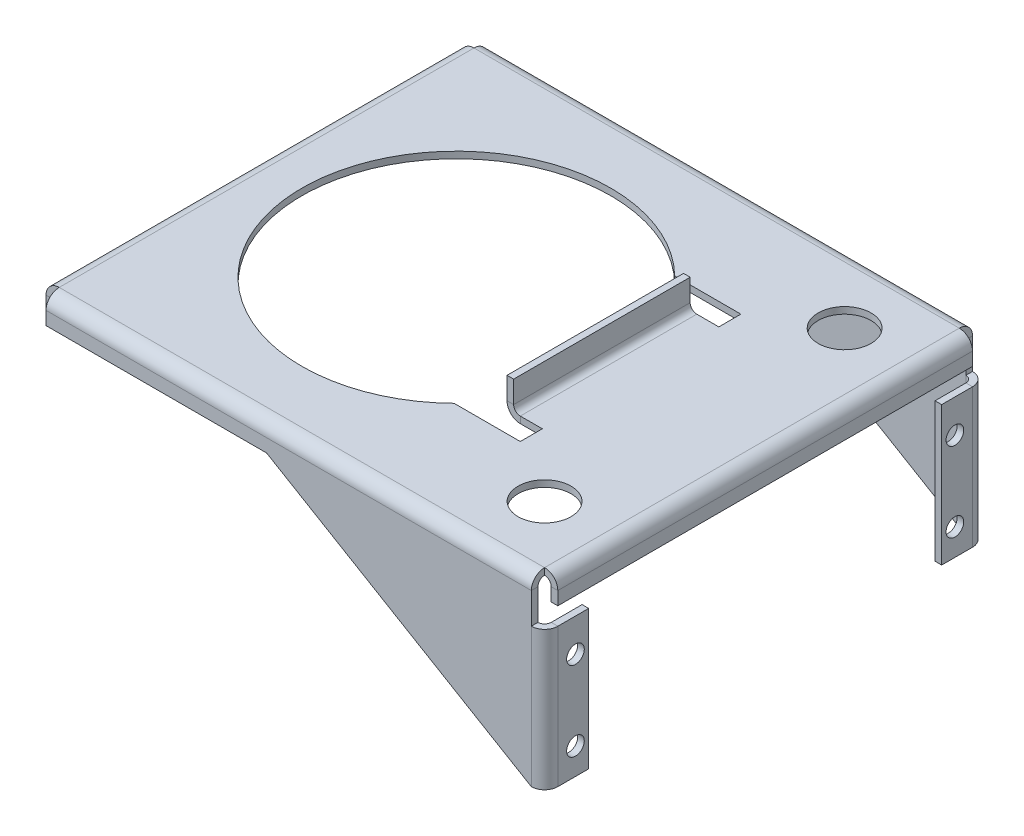
SolidWorks part; units mm, degrees
note: The reader was unsure of these and kept them because the rebuilt part matched: flange length of "Edge-Flange1", "Edge-Flange2", "Edge-Flange3", "Edge-Flange4".
ref_plane "Front Plane" through (0, 0, 0) normal (0, 0, 1) x (1, 0, 0)
ref_plane "Top Plane" through (0, 0, 0) normal (0, 1, 0) x (1, 0, 0)
ref_plane "Right Plane" through (0, 0, 0) normal (1, 0, 0) x (0, 0, -1)
sketch "Sketch1" plane through (0, 0, 0) normal (0, 1, 0) x (1, 0, 0)
  line L0 (-988, 0) -> (49012, 0) construction
  line L1 (-43, -50) -> (67, -50)
  line L2 (-43, -50) -> (-43, 50)
  line L3 (-43, 50) -> (67, 50)
  line L4 (67, -50) -> (67, 50)
  line L5 (-43, -50) -> (67, 50) construction
  line L6 (-43, 50) -> (67, -50) construction
  line L7 (24.4949, -25) -> (39.4949, -25)
  line L9 (24.4949, 25) -> (39.4949, 25)
  line L10 (39.4949, -25) -> (39.4949, -20)
  line L13 (39.4949, 20) -> (31.4949, 20)
  line L14 (31.4949, 20) -> (31.4949, -20)
  line L15 (31.4949, -20) -> (39.4949, -20)
  line L16 (39.4949, 20) -> (39.4949, 25)
  arc A0 (24.4949, 25) -> (24.4949, -25) centre (0, 0) ccw
  point P3 (12, 0)
  point P9 (31.9949, 0)
  dimension "D1" = 70
  dimension "D2" = 100
  dimension "D3" = 110
  dimension "D4" = 43
  dimension "D5" = 50
  dimension "D6" = 15
  dimension "D7" = 8
  dimension "D8" = 5
base flange "Base-Flange1" sketch "Sketch1" thickness 1.5 reverse thickness direction no parameters "D1"=1.5
edge flange "Edge-Flange1" sketch "Sketch12" flange angle 90 flange length 41.5 flange position material inside bend radius 1.5 thickness 1.5 parameters "D6"=10
sketch "Sketch12" plane through (0, -1.5, 50) normal (0, 0, -1) x (1, 0, 0)
  line L2 (-43, 0) -> (-43, 4.5)
  line L4 (67, 40) -> (67, 0)
  line L5 (67, 0) -> (-43, 0) construction
  line L6 (67, 0) -> (-43, 0)
  line L7 (-43, 4.5) -> (7, 4.5)
  line L9 (67, -1.5) -> (-43, -1.5) construction
  line L10 (7, 4.5) -> (67, 40)
  dimension "D1" = 6
  dimension "D2" = 41.5
  dimension "D3" = 50
bend "EdgeBend1" bend radius 1.5 bend angle 90 parameters "D5"=1
edge flange "Edge-Flange2" sketch "Sketch15" flange angle 90 flange length 10 flange position bend outside bend radius 1.5 thickness 1.5 parameters "D6"=10
sketch "Sketch15" plane through (67, 0, 48.5) normal (1, 0, 0) x (0, -1, 0)
  line L2 (10, 0) -> (10, 8.5)
  line L3 (10, 8.5) -> (41.5, 8.5)
  line L4 (41.5, 8.5) -> (41.5, 0)
  line L19 (3, 0) -> (41.5, 0) construction
  line L20 (10, 0) -> (41.5, 0)
  line L22 (0, 1.5) -> (0, 98.5) construction
  dimension "D1" = 10
bend "EdgeBend2" bend radius 1.5 bend angle 90 parameters "D5"=2
hole_wizard "Ø4.0 (4) Diameter Hole1" positions "Sketch16" profile "Sketch17" hole size "Ø4.0" standard "ISO" end condition up to next
sketch "Sketch16" plane through (70, 0, 0) normal (1, 0, 0) x (0, 0, -1)
  line L0 (-47, -41.5) -> (-40, -41.5) construction
  line L1 (-40, -41.5) -> (-40, -10) construction
  point P0 (-43, -17.5)
  point P2 (-43, -35.5)
  point P5 (0, 0)
  dimension "D1" = 6
  dimension "D2" = 18
  dimension "D3" = 3
sketch "Sketch17" plane through (70, -17.5, 43) normal (0, 1, 0) x (0, 0, -1)
  line L0 (0, 0) -> (0, 1.5)
  line L1 (0, 1.5) -> (2, 1.5)
  line L2 (2, 1.5) -> (2, 0)
  line L5 (2, 0) -> (0, 0)
  line L11 (0, -6.35) -> (0, 107.95) construction
  dimension "Thru Hole Dia." = 4
  dimension "Thru Hole Depth" = 1.5
mirror "Mirror1" about plane through (0, 0, 0) normal (0, 0, 1) of "Edge-Flange1", "Edge-Flange2", "Ø4.0 (4) Diameter Hole1"
bend "MirrorBend1" bend radius 1.5 bend angle 90 parameters "D5"=3
bend "MirrorBend2" bend radius 1.5 bend angle 90 parameters "D5"=4
edge flange "Edge-Flange3" sketch "Sketch22" flange profiles "Sketch22", "Sketch24" flange angle 90 flange length 6 flange position bend outside bend radius 1.5 thickness 1.5 parameters "D6"=10, "D8"=1
sketch "Sketch22" plane through (67, -1.5, 0) normal (1, 0, 0) x (0, 0, 1)
  line L2 (-47, 0) -> (-47, 4.5)
  line L3 (-47, 4.5) -> (47, 4.5)
  line L4 (47, 4.5) -> (47, 0)
  line L7 (47, 0) -> (-47, 0) construction
  line L8 (47, 0) -> (-47, 0)
sketch "Sketch24" plane through (-43, -1.5, 0) normal (-1, 0, 0) x (0, 0, -1)
  line L0 (47, 0) -> (-47, 0) construction
  line L1 (47, 0) -> (-47, 0)
  line L2 (-47, 0) -> (-47, 4.5)
  line L3 (-47, 4.5) -> (47, 4.5)
  line L4 (47, 4.5) -> (47, 0)
bend "EdgeBend3" bend radius 1.5 bend angle 90 parameters "D5"=5
bend "EdgeBend4" bend radius 1.5 bend angle 90 parameters "D5"=7
hole_wizard "Ø12.0 (12) Diameter Hole1" positions "Sketch18" profile "Sketch19" hole size "Ø12.0" standard "ISO" end condition up to next
sketch "Sketch18" plane through (0, 0, 0) normal (0, 1, 0) x (1, 0, 0)
  line L0 (-1000, 0) -> (49000, 0) construction
  line L1 (67, -50) -> (-43, -50) construction
  line L2 (70, -47) -> (70, 47) construction
  point P0 (54, 34)
  point P2 (54, -34)
  dimension "D1" = 16
  dimension "D2" = 16
sketch "Sketch19" plane through (54, 0, -34) normal (1, 0, 0) x (0, 0, 1)
  line L0 (0, 0) -> (0, 1.5)
  line L1 (0, 1.5) -> (6, 1.5)
  line L2 (6, 1.5) -> (6, 0)
  line L5 (6, 0) -> (0, 0)
  line L11 (0, -6.35) -> (0, 107.95) construction
  dimension "Thru Hole Dia." = 12
  dimension "Thru Hole Depth" = 1.5
edge flange "Edge-Flange4" sketch "Sketch27" flange angle 90 flange length 6.5 flange position material inside bend radius 1.5 thickness 1.5 parameters "D6"=10
sketch "Sketch27" plane through (31.4949, 0, 0) normal (-1, 0, 0) x (0, 0, 1)
  line L2 (-20, 0) -> (-20, 6.5)
  line L3 (-20, 6.5) -> (20, 6.5)
  line L4 (20, 6.5) -> (20, 0)
  line L7 (20, 0) -> (-20, 0) construction
  line L8 (20, 0) -> (-20, 0)
bend "EdgeBend5" bend radius 1.5 bend angle 90 parameters "D5"=8
sketch "Bend-Lines1" [suppressed] plane through (0, 0, 0) normal (0, 1, 0) x (1, 0, 0)
sketch "Bounding-Box1" [suppressed] plane through (0, 0, 0) normal (0, 1, 0) x (1, 0, 0)
sheet metal parameters "Sheet-Metal1" thickness 1.5 parameters "D1"=2.5
flat pattern "Flat-Pattern1" [suppressed]
sketch "Bend-Lines2" plane through (0, 0, 0) normal (0, 1, 0) x (1, 0, 0)
sketch3d "Bounding-Box2" [suppressed]
  line L0 (-67, 50, 0) -> (43, 50, 0) construction
  line L1 (-67, -50, 0) -> (43, -50, 0) construction
  line L2 (-67, 50, 0) -> (-67, -50, 0) construction
  line L3 (43, 50, 0) -> (43, -50, 0) construction
sheet metal parameters "Sheet-Metal2" thickness 1.5 parameters "D1"=2.5
flat pattern "Flat-Pattern1"
sketch "Bend-Lines2" plane through (0, 0, 0) normal (0, 1, 0) x (1, 0, 0)
  line L0 (-43, -48.5525) -> (67, -48.5525) construction
  line L1 (-43, -48.5525) -> (67, -48.5525) construction
sketch3d "Bounding-Box2" [suppressed]
  line L0 (-43, -88.6051, 0) -> (-43, 50, 0) construction
  line L1 (67, -88.6051, 0) -> (67, 50, 0) construction
  line L2 (-43, -88.6051, 0) -> (67, -88.6051, 0) construction
  line L3 (-43, 50, 0) -> (67, 50, 0) construction
bend of the flat pattern "Flatten-<EdgeBend1>1"
sheet metal parameters "Sheet-Metal3" thickness 1.5 parameters "D1"=2.5
flat pattern "Flat-Pattern1"
sketch "Bend-Lines2" plane through (0, 0, 0) normal (0, 1, 0) x (1, 0, 0)
  line L0 (-43, -48.7671) -> (67, -48.7671) construction
  line L1 (-43, -48.7671) -> (67, -48.7671) construction
  line L2 (65.7671, -88.1652) -> (65.7671, -57.5343) construction
  line L3 (65.7671, -88.1652) -> (65.7671, -57.5343) construction
sketch3d "Bounding-Box2" [suppressed]
  line L0 (-43, -89.0343, 0) -> (-43, 50, 0) construction
  line L1 (74.5343, -89.0343, 0) -> (74.5343, 50, 0) construction
  line L2 (-43, -89.0343, 0) -> (74.5343, -89.0343, 0) construction
  line L3 (-43, 50, 0) -> (74.5343, 50, 0) construction
bend of the flat pattern "Flatten-<EdgeBend1>1"
bend of the flat pattern "Flatten-<EdgeBend2>1"
sheet metal parameters "Sheet-Metal4" thickness 1.5 parameters "D1"=2.5
flat pattern "Flat-Pattern1"
sketch "Bend-Lines2" plane through (0, 0, 0) normal (0, 1, 0) x (1, 0, 0)
  line L0 (-43, -48.7671) -> (67, -48.7671) construction
  line L1 (-43, -48.7671) -> (67, -48.7671) construction
  line L2 (65.7671, -88.1652) -> (65.7671, -57.5343) construction
  line L3 (65.7671, -88.1652) -> (65.7671, -57.5343) construction
sketch3d "Bounding-Box2" [suppressed]
  line L0 (-43, -89.0343, 0) -> (-43, 50, 0) construction
  line L1 (74.5343, -89.0343, 0) -> (74.5343, 50, 0) construction
  line L2 (-43, -89.0343, 0) -> (74.5343, -89.0343, 0) construction
  line L3 (-43, 50, 0) -> (74.5343, 50, 0) construction
bend of the flat pattern "Flatten-<EdgeBend1>1"
bend of the flat pattern "Flatten-<EdgeBend2>1"
sheet metal parameters "Sheet-Metal5" thickness 1.5 parameters "D1"=2.5
flat pattern "Flat-Pattern1"
sketch "Bend-Lines2" plane through (0, 0, 0) normal (0, 1, 0) x (1, 0, 0)
  line L0 (-43, -48.7671) -> (67, -48.7671) construction
  line L1 (-43, -48.7671) -> (67, -48.7671) construction
  line L2 (65.7671, -88.1652) -> (65.7671, -57.5343) construction
  line L3 (65.7671, -88.1652) -> (65.7671, -57.5343) construction
  line L4 (65.7671, 57.5343) -> (65.7671, 88.1652) construction
  line L5 (67, 48.7671) -> (-43, 48.7671) construction
  line L6 (65.7671, 57.5343) -> (65.7671, 88.1652) construction
  line L7 (67, 48.7671) -> (-43, 48.7671) construction
sketch3d "Bounding-Box2" [suppressed]
  line L0 (-43, -89.0343, 0) -> (-43, 89.0343, 0) construction
  line L1 (74.5343, -89.0343, 0) -> (74.5343, 89.0343, 0) construction
  line L2 (-43, -89.0343, 0) -> (74.5343, -89.0343, 0) construction
  line L3 (-43, 89.0343, 0) -> (74.5343, 89.0343, 0) construction
bend of the flat pattern "Flatten-<EdgeBend1>1"
bend of the flat pattern "Flatten-<EdgeBend2>1"
bend of the flat pattern "Flatten-<MirrorBend1>1"
bend of the flat pattern "Flatten-<MirrorBend2>1"
sheet metal parameters "Sheet-Metal6" thickness 1.5 parameters "D1"=2.5
flat pattern "Flat-Pattern1"
sketch "Bend-Lines2" plane through (0, 0, 0) normal (0, 1, 0) x (1, 0, 0)
  line L0 (-43, -51.7671) -> (67, -51.7671) construction
  line L1 (-43, -51.7671) -> (67, -51.7671) construction
  line L2 (68.7671, -92.0343) -> (68.7671, -60.5343) construction
  line L3 (68.7671, -92.0343) -> (68.7671, -60.5343) construction
  line L4 (68.7671, 60.5343) -> (68.7671, 92.0343) construction
  line L5 (67, 51.7671) -> (-43, 51.7671) construction
  line L6 (68.7671, 60.5343) -> (68.7671, 92.0343) construction
  line L7 (67, 51.7671) -> (-43, 51.7671) construction
  line L8 (-44.7671, 50) -> (-44.7671, -50) construction
  line L9 (68.7671, -50) -> (68.7671, 50) construction
  line L10 (-44.7671, 50) -> (-44.7671, -50) construction
  line L11 (68.7671, -50) -> (68.7671, 50) construction
sketch3d "Bounding-Box2" [suppressed]
  line L0 (-49.5343, -92.0343, 0) -> (-49.5343, 92.0343, 0) construction
  line L1 (77.5343, -92.0343, 0) -> (77.5343, 92.0343, 0) construction
  line L2 (-49.5343, -92.0343, 0) -> (77.5343, -92.0343, 0) construction
  line L3 (-49.5343, 92.0343, 0) -> (77.5343, 92.0343, 0) construction
bend of the flat pattern "Flatten-<EdgeBend1>1"
bend of the flat pattern "Flatten-<EdgeBend2>1"
bend of the flat pattern "Flatten-<MirrorBend1>1"
bend of the flat pattern "Flatten-<MirrorBend2>1"
bend of the flat pattern "Flatten-<EdgeBend4>2"
bend of the flat pattern "Flatten-<EdgeBend3>2"
sheet metal parameters "Sheet-Metal7" thickness 1.5 parameters "D1"=2.5
flat pattern "Flat-Pattern1"
sketch "Bend-Lines2" plane through (0, 0, 0) normal (0, 1, 0) x (1, 0, 0)
  line L0 (-43, -51.7671) -> (67, -51.7671) construction
  line L1 (-43, -51.7671) -> (67, -51.7671) construction
  line L2 (68.7671, -92.0343) -> (68.7671, -60.5343) construction
  line L3 (68.7671, -92.0343) -> (68.7671, -60.5343) construction
  line L4 (68.7671, 60.5343) -> (68.7671, 92.0343) construction
  line L5 (67, 51.7671) -> (-43, 51.7671) construction
  line L6 (68.7671, 60.5343) -> (68.7671, 92.0343) construction
  line L7 (67, 51.7671) -> (-43, 51.7671) construction
  line L8 (68.7671, -50) -> (68.7671, 50) construction
  line L9 (68.7671, -50) -> (68.7671, 50) construction
  line L10 (-44.7671, 50) -> (-44.7671, -50) construction
  line L11 (-44.7671, 50) -> (-44.7671, -50) construction
sketch3d "Bounding-Box2" [suppressed]
  line L0 (-49.5343, -92.0343, 0) -> (-49.5343, 92.0343, 0) construction
  line L1 (77.5343, -92.0343, 0) -> (77.5343, 92.0343, 0) construction
  line L2 (-49.5343, -92.0343, 0) -> (77.5343, -92.0343, 0) construction
  line L3 (-49.5343, 92.0343, 0) -> (77.5343, 92.0343, 0) construction
bend of the flat pattern "Flatten-<EdgeBend1>1"
bend of the flat pattern "Flatten-<EdgeBend2>1"
bend of the flat pattern "Flatten-<MirrorBend1>1"
bend of the flat pattern "Flatten-<MirrorBend2>1"
bend of the flat pattern "Flatten-<EdgeBend3>1"
bend of the flat pattern "Flatten-<EdgeBend4>1"
sheet metal parameters "Sheet-Metal8" thickness 1.5 parameters "D1"=2.5
flat pattern "Flat-Pattern1"
sketch "Bend-Lines2" plane through (0, 0, 0) normal (0, 1, 0) x (1, 0, 0)
  line L0 (-43, -48.7671) -> (67, -48.7671) construction
  line L1 (-43, -48.7671) -> (67, -48.7671) construction
  line L2 (68.7671, -89.0343) -> (68.7671, -57.5343) construction
  line L3 (68.7671, -89.0343) -> (68.7671, -57.5343) construction
  line L4 (68.7671, 57.5343) -> (68.7671, 89.0343) construction
  line L5 (67, 48.7671) -> (-43, 48.7671) construction
  line L6 (68.7671, 57.5343) -> (68.7671, 89.0343) construction
  line L7 (67, 48.7671) -> (-43, 48.7671) construction
  line L8 (-44.7671, 47) -> (-44.7671, -47) construction
  line L9 (68.7671, -47) -> (68.7671, 47) construction
  line L10 (-44.7671, 47) -> (-44.7671, -47) construction
  line L11 (68.7671, -47) -> (68.7671, 47) construction
  line L12 (32.7278, 20) -> (32.7278, -20) construction
  line L13 (32.7278, 20) -> (32.7278, -20) construction
sketch3d "Bounding-Box2" [suppressed]
  line L0 (-49.5343, -89.0343, 0) -> (-49.5343, 89.0343, 0) construction
  line L1 (77.5343, -89.0343, 0) -> (77.5343, 89.0343, 0) construction
  line L2 (-49.5343, -89.0343, 0) -> (77.5343, -89.0343, 0) construction
  line L3 (-49.5343, 89.0343, 0) -> (77.5343, 89.0343, 0) construction
bend of the flat pattern "Flatten-<EdgeBend1>1"
bend of the flat pattern "Flatten-<EdgeBend2>1"
bend of the flat pattern "Flatten-<MirrorBend1>1"
bend of the flat pattern "Flatten-<MirrorBend2>1"
bend of the flat pattern "Flatten-<EdgeBend4>2"
bend of the flat pattern "Flatten-<EdgeBend3>2"
bend of the flat pattern "Flatten-<EdgeBend5>1"
